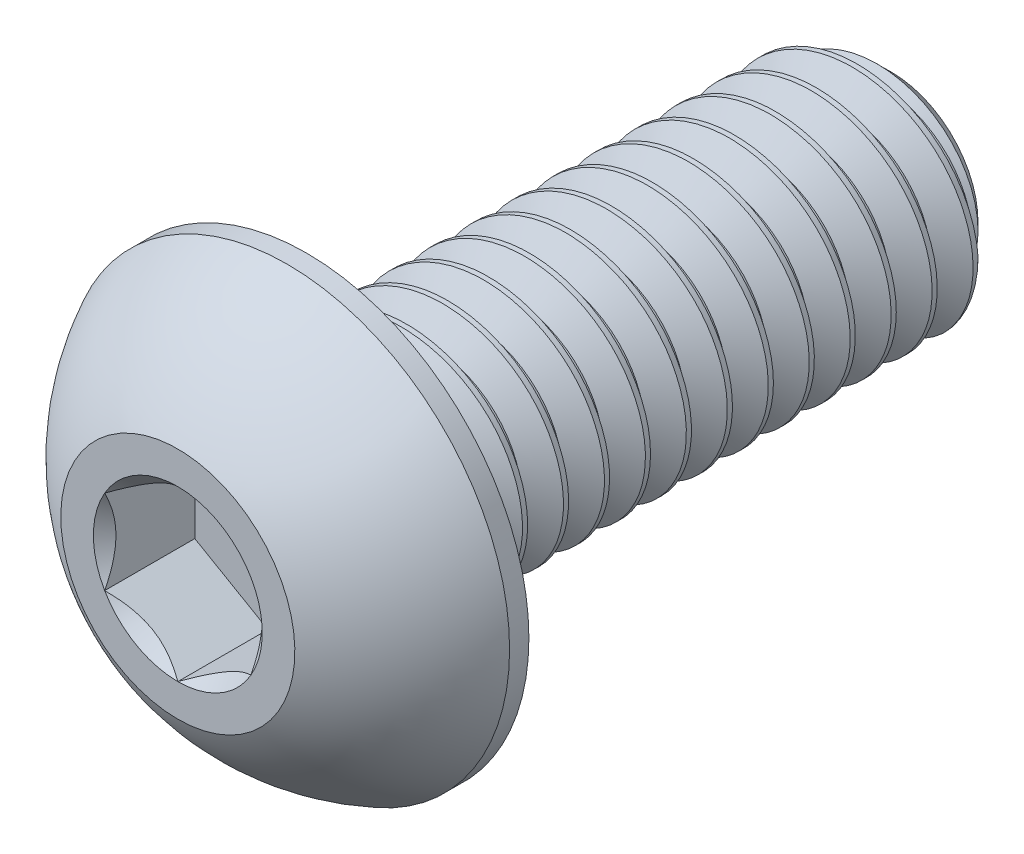
SolidWorks part; units mm, degrees
material "Alloy Steel"
ref_plane "Front" through (0, 0, 0) normal (0, 0, 1) x (1, 0, 0)
ref_plane "Top" through (0, 0, 0) normal (0, 1, 0) x (1, 0, 0)
ref_plane "Right" through (0, 0, 0) normal (1, 0, 0) x (0, 0, -1)
sketch "Sketch1" plane through (0, 0, 0) normal (1, 0, 0) x (0, 0, -1)
  line L2 (2.2, 2) -> (12.2, 2)
  line L3 (12.2, 2) -> (12.2, 0)
  line L4 (12.2, 0) -> (2.2, 0)
  line L6 (1.87, 3.8) -> (2.2, 3.8) construction
  line L7 (12.2, 2) -> (12.2, -2) construction
  line L8 (0, 0) -> (2.2, 0) construction
  line L9 (2.2, 3.8) -> (2.2, -3.8) construction
  line L11 (2.2, 2) -> (2.2, 0)
  line L13 (0, 1.25) -> (0, -1.25) construction
  line L14 (0, 1.25) -> (0, 2) construction
  arc A3 (0, 2) -> (1.87, 3.8) centre (3.7264, 0) cw construction
  dimension "D1" = 0.33
  dimension "Head Ht" = 2.2
  dimension "Head Dia" = 7.6
  dimension "Dia" = 4
  dimension "Lg" = 10
  dimension "Hex" = 2.5
revolve "Revolve1" add sketch "Sketch1" angle 360 mid plane about L4
sketch "Sketch3" plane through (0, 0, -12.2) normal (0, 0, -1) x (-1, 0, 0)
  circle A0 centre (0, 0) radius 2
curve "Helix/Spiral1" pitch 0.7 height 10.7 radius 2 centre (0, 0, -12.2) axis (0, 0, 1) start towards (0, 1, 0)
sketch "Sketch2" plane through (0, 0, 0) normal (1, 0, 0) x (0, 0, -1)
  line L0 (12.2, 2) -> (12.8125, 2)
  line L1 (12.8125, 2) -> (12.55, 1.5453)
  line L2 (12.55, 1.5453) -> (12.4625, 1.5453)
  line L3 (12.4625, 1.5453) -> (12.2, 2)
  line L4 (12.3312, 1.7727) -> (12.6812, 1.7727) construction
  dimension "D1" = 60
  dimension "D2" = 0.0875
  dimension "D3" = 0.35
chamfer "Chamfer1" distance 0.525 angle 45 1 edges at (0, 2, -12.2)
sweep "Cut-Sweep1" cut profiles "Sketch2" path "Helix/Spiral1"
sketch "Sketch7" plane through (0, 0, 0) normal (1, 0, 0) x (0, 0, -1)
  line L6 (1.87, 3.8) -> (2.2, 3.8) construction
  line L8 (0, 0) -> (2.2, 0) construction
  line L11 (2.2, 3.8) -> (2.2, -3.8) construction
  line L12 (1.87, 3.8) -> (2.2, 3.8)
  line L13 (0, 0) -> (2.2, 0)
  line L14 (0, 1.25) -> (0, -1.25) construction
  line L15 (2.2, 3.8) -> (2.2, 0)
  line L16 (0, 2) -> (0, 0)
  arc A2 (1.87, 3.8) -> (0, 2) centre (3.7264, 0) ccw construction
  arc A3 (1.87, 3.8) -> (0, 2) centre (3.7264, 0) ccw
revolve "Revolve2" add sketch "Sketch7" angle 360 mid plane about L13
sketch "Sketch5" plane through (0, 0, 0) normal (0, 0, 1) x (1, 0, 0)
  line L1 (1.25, -0.7217) -> (1.25, 0.7217)
  line L2 (1.25, 0.7217) -> (0, 1.4434)
  line L3 (0, 1.4434) -> (-1.25, 0.7217)
  line L4 (-1.25, 0.7217) -> (-1.25, -0.7217)
  line L5 (-1.25, -0.7217) -> (0, -1.4434)
  line L6 (0, -1.4434) -> (1.25, -0.7217)
  circle A0 centre (0, 0) radius 1.25 construction
extrude "Cut-Extrude2" cut sketch "Sketch5" against normal blind 1.54
sketch "Sketch6" plane through (0, 0, 0) normal (0, 0, 1) x (1, 0, 0)
  circle A0 centre (0, 0) radius 1.4434
extrude "Cut-Extrude3" cut sketch "Sketch6" against normal blind 1.54 draft 45
sketch "Sketch9" [suppressed] plane through (0, 0, -6.6) normal (0, 0, 1) x (1, 0, 0)
  circle A2 centre (0, 0) radius 6
extrude "Boss-Extrude2" [suppressed] add sketch "Sketch9" against normal offset from surface (19 mm away) 32 up to face at (0, 1.475, -12.2)
sketch "Sketch10" plane through (0, 0, 0) normal (1, 0, 0) x (0, 0, -1)
  line L0 (12.2, 2) -> (12.2, -2) construction
  point P0 (11.15, -2)
  dimension "D1" = 1.05
equation "\"D3@Helix/Spiral1\" = \"Lg@Sketch1\" + \"D4@Helix/Spiral1\""
equation "\"D2@Sketch2\" = \"D4@Helix/Spiral1\" * .125"
equation "\"D3@Sketch2\" = \"D4@Helix/Spiral1\" * .5"
equation "\"D1@Chamfer1\" = \"D4@Helix/Spiral1\" * .75"
equation "\"D1@Cut-Extrude2\" = \"Head Ht@Sketch1\" * .7"
equation "\"D1@Sketch1\" = \"Head Ht@Sketch1\" * .15"
equation "\"D1@Sketch10\" = \"D4@Helix/Spiral1\" * 1.5"
equation "\"D1@Cut-Extrude3\" = \"D1@Cut-Extrude2\""
